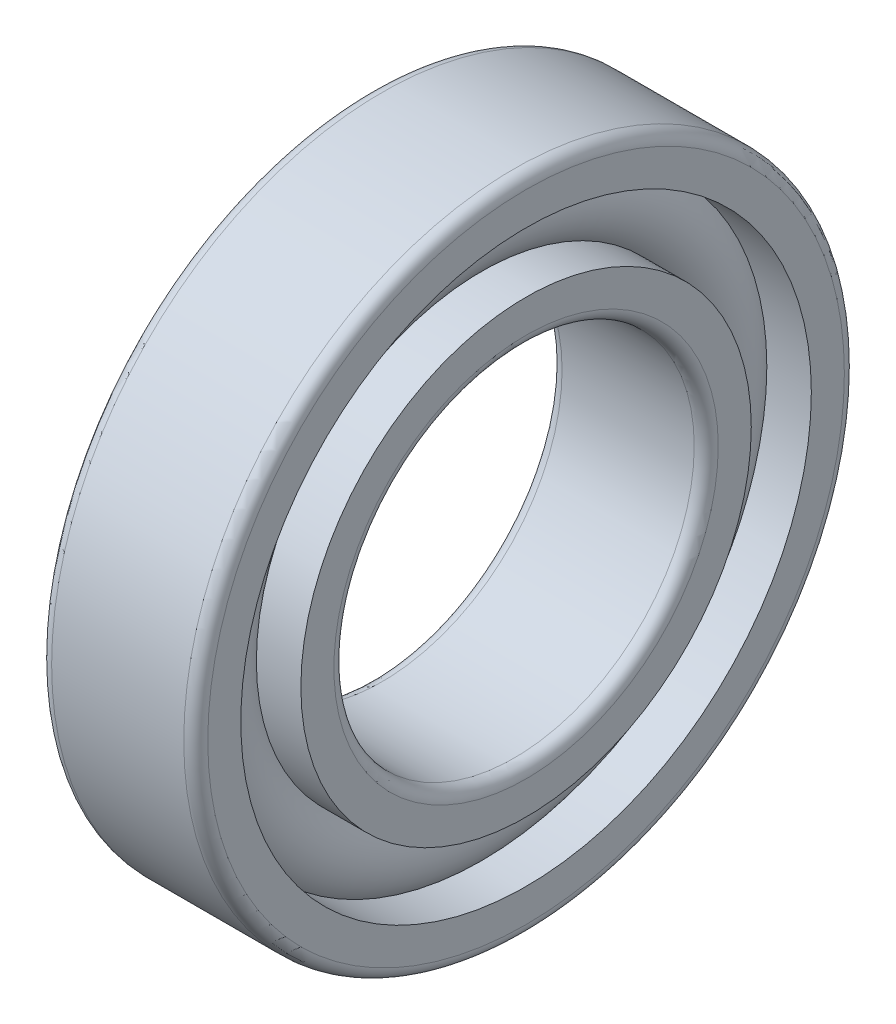
SolidWorks part; units mm, degrees
ref_plane "Plane1" through (0, 0, 0) normal (0, 0, 1) x (1, 0, 0)
ref_plane "Plane2" through (0, 0, 0) normal (0, 1, 0) x (1, 0, 0)
ref_plane "Plane3" through (0, 0, 0) normal (1, 0, 0) x (0, 0, -1)
sketch "Clipboard" plane through (0, 0, 0) normal (0, 0, 1) x (1, 0, 0)
  line L0 (-10, 0) -> (10, 0) construction
  line L1 (0, 0) -> (22.3471, -0.7804)
  line L2 (0, 0) -> (21.2371, 0.7416)
  line L3 (0, 0) -> (22.3471, -0.7804)
  line L4 (0, 0) -> (-22.3573, -0.3902)
  dimension "BallCLRad" = 21.25
sketch "CagSpiSke" plane through (0, 0, 0) normal (0, 0, 1) x (1, 0, 0)
  line L0 (0.375, 20.625) -> (0.375, 21.875)
  line L1 (0.375, 21.875) -> (-0.375, 21.875)
  line L2 (-0.375, 21.875) -> (-0.375, 20.625)
  line L3 (-0.375, 20.625) -> (0.375, 20.625)
  line L4 (-20.6375, 0) -> (20.6375, 0) construction
  line L5 (0, 0) -> (0, 23.7692) construction
  dimension "OD" = 43.75
  dimension "ID" = 41.25
revolve "CageSpine" add sketch "CagSpiSke" angle 0.001 about L4 reverse direction yes
ref_axis "Axis1" through (-50, 0, 0) along (1, 0, 0)
sketch "CagBalSke" plane through (0, 0, 0) normal (0, 0, 1) x (1, 0, 0)
  line L0 (-4.125, 21.25) -> (4.125, 21.25)
  line L1 (-1.905, 21.25) -> (1.905, 21.25) construction
  line L2 (-10, 0) -> (10, 0) construction
  line L3 (0, 0) -> (0, 24) construction
  arc A0 (4.125, 21.25) -> (-4.125, 21.25) centre (0, 21.25) cw
  dimension "BallCLRad" = 21.25
revolve "CageBall" [suppressed] add sketch "CagBalSke" angle 360 about L1 reverse direction yes
pattern_circular "CageBalls" [suppressed] count 2 every 180 about axis through (-50, 0, 0) along (1, 0, 0)
sketch "CagTrmODSke" plane through (0, 0, 0) normal (0, 0, 1) x (1, 0, 0)
  line L0 (4.126, 21.875) -> (4.126, 25.376)
  line L1 (4.126, 25.376) -> (-4.126, 25.376)
  line L2 (-4.126, 25.376) -> (-4.126, 21.875)
  line L3 (-4.126, 21.875) -> (4.126, 21.875)
  line L4 (-20.6375, 0) -> (20.6375, 0) construction
  line L5 (0, 0) -> (0, 25) construction
  dimension "Width" = 8.252
  dimension "ID" = 43.75
  dimension "OD" = 50.752
revolve "CageTrimOD" [suppressed] cut sketch "CagTrmODSke" angle 360 about L4 reverse direction yes
sketch "CagTrmIDSke" plane through (0, 0, 0) normal (0, 0, 1) x (1, 0, 0)
  line L0 (4.126, 17.126) -> (4.126, 20.625)
  line L1 (4.126, 20.625) -> (-4.126, 20.625)
  line L2 (-4.126, 20.625) -> (-4.126, 17.126)
  line L3 (-4.126, 17.126) -> (4.126, 17.126)
  line L4 (-20.6375, 0) -> (20.6375, 0) construction
  line L5 (0, 0) -> (0, 25) construction
  dimension "Width" = 8.252
  dimension "ID" = 34.252
  dimension "OD" = 41.25
revolve "CageTrimID" [suppressed] cut sketch "CagTrmIDSke" angle 360 about L4 reverse direction yes
sketch "BalSimSke" plane through (0, 0, 0) normal (0, 0, 1) x (1, 0, 0)
  line L0 (-10, 0) -> (10, 0) construction
  line L1 (-10, 21.25) -> (10, 21.25) construction
  line L2 (0, 0) -> (0, 23) construction
  circle A0 centre (0, 21.25) radius 3.75
  dimension "BallCLRad" = 21.25
  dimension "Ball_diameter" = 7.5
revolve "BallsSimplified" add sketch "BalSimSke" angle 360 about L0
sketch "BalDetSke" plane through (0, 0, 0) normal (0, 0, 1) x (1, 0, 0)
  line L0 (-3.75, 21.25) -> (3.75, 21.25)
  line L1 (-1.905, 21.25) -> (1.905, 21.25) construction
  line L2 (0, 0) -> (0, 25) construction
  arc A0 (3.75, 21.25) -> (-3.75, 21.25) centre (0, 21.25) cw
  dimension "BallCLRad" = 21.25
  dimension "Ball_diameter" = 7.5
revolve "BallDetailed" [suppressed] add sketch "BalDetSke" angle 360 about L1 reverse direction yes
sketch "InnRacSke" plane through (0, 0, 0) normal (0, 0, 1) x (1, 0, 0)
  line L0 (-2.7615, 18.75) -> (-6.5, 18.75)
  line L1 (-6.5, 18.75) -> (-6.5, 16)
  line L2 (-5.5, 15) -> (5.5, 15)
  line L3 (6.5, 16) -> (6.5, 18.75)
  line L4 (6.5, 18.75) -> (2.7615, 18.75)
  line L5 (-20.6375, 0) -> (20.6375, 0) construction
  line L6 (0, 0) -> (0, 30) construction
  arc A0 (-6.5, 16) -> (-5.5, 15) centre (-5.5, 16) ccw
  arc A1 (5.5, 15) -> (6.5, 16) centre (5.5, 16) ccw
  arc A2 (2.7615, 18.75) -> (-2.7615, 18.75) centre (0, 21.25) cw
  dimension "BallCLRad" = 21.25
  dimension "Fillet_radius" = 1
  dimension "Ball_diameter" = 7.45
  dimension "ID" = 30
  dimension "OD" = 37.5
  dimension "Width" = 13
revolve "InnerRace" add sketch "InnRacSke" angle 360 about L5 reverse direction yes
sketch "OutRacSke" plane through (0, 0, 0) normal (0, 0, 1) x (1, 0, 0)
  line L0 (-2.7615, 23.75) -> (-6.5, 23.75)
  line L1 (-6.5, 23.75) -> (-6.5, 26.5)
  line L2 (-5.5, 27.5) -> (5.5, 27.5)
  line L3 (6.5, 26.5) -> (6.5, 23.75)
  line L4 (6.5, 23.75) -> (2.7615, 23.75)
  line L5 (-20.6375, 0) -> (20.6375, 0) construction
  line L6 (0, 0) -> (0, 30) construction
  arc A0 (-6.5, 26.5) -> (-5.5, 27.5) centre (-5.5, 26.5) cw
  arc A1 (5.5, 27.5) -> (6.5, 26.5) centre (5.5, 26.5) cw
  arc A2 (2.7615, 23.75) -> (-2.7615, 23.75) centre (0, 21.25) ccw
  dimension "BallCLRad" = 21.25
  dimension "Fillet_radius" = 1
  dimension "Ball_diameter" = 7.45
  dimension "Width" = 13
revolve "OuterRace" add sketch "OutRacSke" angle 360 about L5 reverse direction yes
pattern_circular "BallsDetailed" [suppressed] count 2 every 180 about axis through (-50, 0, 0) along (1, 0, 0)
equation "\"BallCLRad@Clipboard\" = ( \"OD@OutRacSke\" + \"ID@InnRacSke\" ) / 4"
equation "\"BallCLRad@BalSimSke\" = \"BallCLRad@Clipboard\""
equation "\"BallCLRad@BalDetSke\" = \"BallCLRad@Clipboard\""
equation "\"BallCLRad@InnRacSke\" = \"BallCLRad@Clipboard\""
equation "\"BallCLRad@OutRacSke\" = \"BallCLRad@Clipboard\""
equation "\"Ball_diameter@InnRacSke\" = \"Ball_diameter@BalDetSke\" - 0.05"
equation "\"Ball_diameter@OutRacSke\" = \"Ball_diameter@BalDetSke\" - 0.05"
equation "\"Ball_diameter@BalSimSke\" = \"Ball_diameter@BalDetSke\""
equation "\"Width@OutRacSke\" = \"Width@InnRacSke\""
equation "\"Fillet_radius@OutRacSke\" = \"Fillet_radius@InnRacSke\""
equation "\"Max_count@Clipboard\" = int( 3.14159265 / atn(( \"Ball_diameter@BalDetSke\" / 2) / sqr( \"BallCLRad@Clipboard\"  *  \"BallCLRad@Clipboard\" - ( \"Ball_diameter@BalDetSke\" / 2) *  ( \"Ball_diameter@BalDetSke\" / 2))))"
equation "\"Max_count@Clipboard\" = ((sgn( \"Max_count@Clipboard\" - \"Count@Clipboard\" )-1)*( \"Max_count@Clipboard\" - \"Count@Clipboard\" ))/-2+ \"Count@Clipboard\""
equation "\"Count@BallsDetailed\" = int( \"Show_count@Clipboard\" ) "
equation "\"Count@BallsDetailed\" = ((sgn( \"Count@BallsDetailed\" - \"Max_count@Clipboard\" )-1)*( \"Count@BallsDetailed\" - \"Max_count@Clipboard\" ))/-2+ \"Max_count@Clipboard\""
equation "\"Count@BallsDetailed\" = ((sgn( \"Count@BallsDetailed\" - \"Min_count@Clipboard\" )+1)*( \"Count@BallsDetailed\" - \"Min_count@Clipboard\"))/2 +\"Min_count@Clipboard\""
equation "\"Angle@BallsDetailed\" = 360.0 / \"Max_count@Clipboard\""
equation "\"BallCLRad@CagBalSke\" = \"BallCLRad@Clipboard\""
equation "\"Count@CageBalls\" = \"Count@BallsDetailed\""
equation "\"Angle@CageBalls\" = \"Angle@BallsDetailed\""
equation "\"Angle@CageSpine\" =  \"Angle@CageBalls\" * ( \"Count@CageBalls\" -1 + int( \"Count@CageBalls\" / \"Max_count@Clipboard\" ) )  + 0.001 -  int( \"Count@CageBalls\" / \"Max_count@Clipboard\" ) * 0.001"
equation "\"Angle@CageSpine\" =  \"Angle@CageSpine\" * int( \"Min_count@Clipboard\" / 2) + int(1 / \"Min_count@Clipboard\")  * 0.001"
equation "\"CageWallOD@CagBalSke\" =  \"Ball_diameter@BalDetSke\" * 1.1"
equation "\"Thickness@CagSpiSke\" =  \"Ball_diameter@BalDetSke\" * 0.1"
equation "\"OD@CagTrmODSke\" = \"BallCLRad@Clipboard\" * 2 + \"CageWallOD@CagBalSke\" + 0.002"
equation "\"ID@CagTrmODSke\" = \"BallCLRad@Clipboard\" * 2 + \"Ball_diameter@BalDetSke\" / 6"
equation "\"OD@CagTrmIDSke\" = \"BallCLRad@Clipboard\" * 2 - \"Ball_diameter@BalDetSke\" / 6"
equation "\"ID@CagTrmIDSke\" = \"BallCLRad@Clipboard\" * 2 - \"CageWallOD@CagBalSke\" + 0.002"
equation "\"OD@CagSpiSke\" = \"ID@CagTrmODSke\""
equation "\"ID@CagSpiSke\" = \"OD@CagTrmIDSke\""
equation "\"Width@CagTrmODSke\" = \"CageWallOD@CagBalSke\" + 0.002"
equation "\"Width@CagTrmIDSke\" = \"CageWallOD@CagBalSke\" + 0.002"
